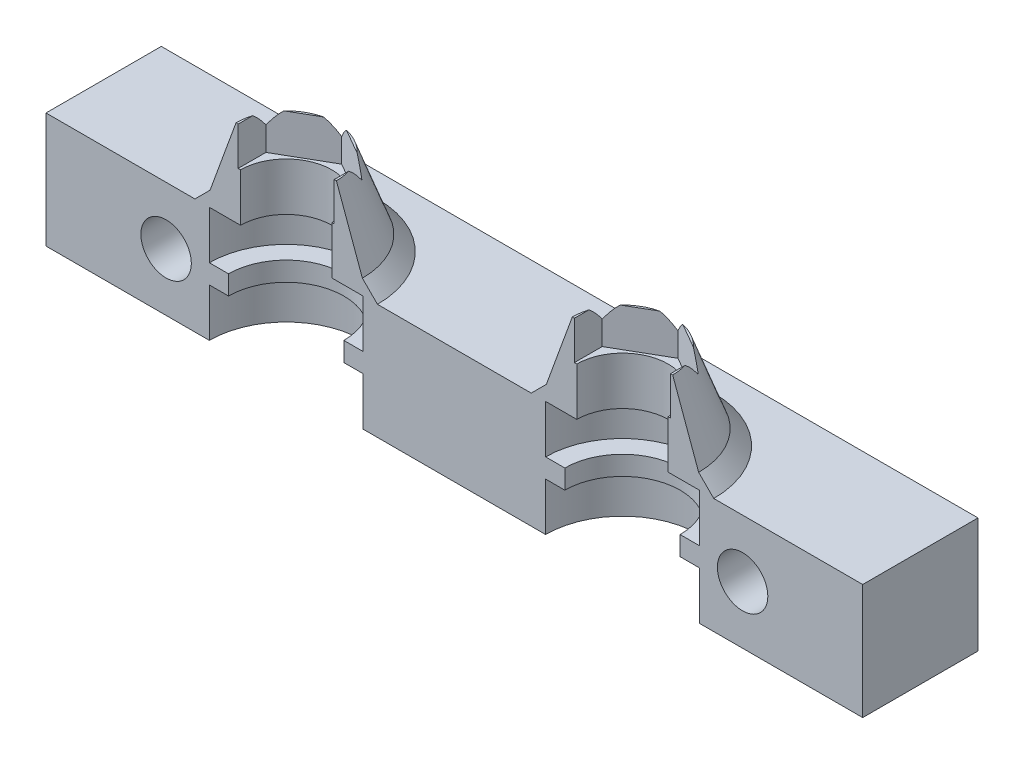
SolidWorks part; units mm, degrees
ref_plane "Front Plane" through (0, 0, 0) normal (0, 0, 1) x (1, 0, 0)
ref_plane "Top Plane" through (0, 0, 0) normal (0, 1, 0) x (1, 0, 0)
ref_plane "Right Plane" through (0, 0, 0) normal (1, 0, 0) x (0, 0, -1)
sketch "Sketch1" plane through (0, 0, 0) normal (0, 0, 1) x (1, 0, 0)
  line L1 (-42.5, -6) -> (42.5, -6)
  line L2 (-42.5, -6) -> (-42.5, 6)
  line L3 (-42.5, 6) -> (42.5, 6)
  line L4 (42.5, -6) -> (42.5, 6)
  line L5 (-42.5, -6) -> (42.5, 6) construction
  line L6 (-42.5, 6) -> (42.5, -6) construction
  point P0 (0, 0)
  dimension "D1" = 85
  dimension "D2" = 12
extrude "Boss-Extrude1" add sketch "Sketch1" along normal blind 12
sketch "Sketch2" plane through (0, 6, 0) normal (0, 1, 0) x (1, 0, 0)
  line L0 (42.5, -12) -> (-42.5, -12) construction
  line L1 (-42.5, -12) -> (-42.5, 0) construction
  line L2 (42.5, -12) -> (42.5, 0) construction
  circle A0 centre (-17.5, -12) radius 8
  circle A1 centre (17.5, -12) radius 8
  dimension "D1" = 16
  dimension "D2" = 16
  dimension "D3" = 25
  dimension "D4" = 25
extrude "Cut-Extrude2" cut sketch "Sketch2" against normal blind 5
sketch "Sketch3" plane through (0, -6, 0) normal (0, -1, 0) x (1, 0, 0)
  line L0 (-42.5, 12) -> (42.5, 12) construction
  line L1 (-42.5, 12) -> (-42.5, 0) construction
  line L2 (42.5, 12) -> (42.5, 0) construction
  circle A0 centre (-17.5, 12) radius 8
  circle A1 centre (17.5, 12) radius 8
  dimension "D1" = 16
  dimension "D2" = 16
  dimension "D3" = 25
  dimension "D4" = 25
extrude "Cut-Extrude3" cut sketch "Sketch3" against normal blind 5
sketch "Sketch4" plane through (0, 0, 0) normal (0, 1, 0) x (1, 0, 0)
  line L0 (-25.5, -12) -> (-9.5, -12) construction
  line L1 (9.5, -12) -> (25.5, -12) construction
  circle A0 centre (-17.5, -12) radius 6
  circle A1 centre (17.5, -12) radius 6
  dimension "D1" = 12
  dimension "D2" = 12
extrude "Cut-Extrude4" cut sketch "Sketch4" against normal through all both and the other way through all
sketch "Sketch5" plane through (0, 0, 12) normal (0, 0, 1) x (1, 0, 0)
  line L0 (-42.5, 0) -> (-30, 0) construction
  line L1 (-42.5, 6) -> (-42.5, -6) construction
  line L2 (42.5, 0) -> (30, 0) construction
  line L3 (42.5, -6) -> (42.5, 6) construction
  circle A0 centre (-30, 0) radius 2.625
  circle A1 centre (30, 0) radius 2.625
  dimension "D3" = 5.25
  dimension "D4" = 5.25
  dimension "D1" = 12.5
  dimension "D2" = 12.5
  dimension "D5" = 60
extrude "Cut-Extrude6" cut sketch "Sketch5" against normal through all
sketch "Sketch7" plane through (0, 6, 0) normal (0, 1, 0) x (1, 0, 0)
  circle A0 centre (-17.5, -12) radius 8.5
  circle A1 centre (17.5, -12) radius 8.5
  dimension "D1" = 17
  dimension "D2" = 17
extrude "Boss-Extrude3" add sketch "Sketch7" along normal blind 9 draft 20
chamfer "Chamfer1" distance 1 angle 45 1 edges at (-17.5, 6, 3.5) first distance on face at (0, 6, 6.875)
chamfer "Chamfer2" distance 1 angle 45 1 edges at (17.5, 6, 3.5) first distance on face at (0, 6, 6.75)
sketch "Sketch10" plane through (0, 15, 0) normal (0, 1, 0) x (1, 0, 0)
  line L1 (-17.5, -6.2265) -> (-22.5, -9.1132)
  line L2 (-22.5, -9.1132) -> (-22.5, -14.8868)
  line L3 (-22.5, -14.8868) -> (-17.5, -17.7735)
  line L4 (-17.5, -17.7735) -> (-12.5, -14.8868)
  line L5 (-12.5, -14.8868) -> (-12.5, -9.1132)
  line L6 (-12.5, -9.1132) -> (-17.5, -6.2265)
  line L7 (17.5, -6.2265) -> (12.5, -9.1132)
  line L8 (12.5, -9.1132) -> (12.5, -14.8868)
  line L9 (12.5, -14.8868) -> (17.5, -17.7735)
  line L10 (17.5, -17.7735) -> (22.5, -14.8868)
  line L11 (22.5, -14.8868) -> (22.5, -9.1132)
  line L12 (22.5, -9.1132) -> (17.5, -6.2265)
  circle A0 centre (-17.5, -12) radius 5 construction
  circle A1 centre (17.5, -12) radius 5 construction
  dimension "D1" = 10
  dimension "D2" = 10
extrude "Cut-Extrude9" cut sketch "Sketch10" against normal blind 4
sketch "Sketch11" plane through (0, 11, 0) normal (0, 1, 0) x (1, 0, 0)
  circle A0 centre (-17.5, -12) radius 4.75
  circle A1 centre (17.5, -12) radius 4.75
  dimension "D1" = 9.5
  dimension "D2" = 9.5
extrude "Cut-Extrude10" cut sketch "Sketch11" against normal through all
sketch "Sketch12" plane through (0, -6, 0) normal (0, -1, 0) x (1, 0, 0)
  line L1 (-42.5, 12) -> (42.2762, 12)
  line L2 (-42.5, 12) -> (-42.5, 21.8174)
  line L3 (-42.5, 21.8174) -> (42.2762, 21.8174)
  line L4 (42.2762, 12) -> (42.2762, 21.8174)
extrude "Cut-Extrude11" cut sketch "Sketch12" against normal through all
